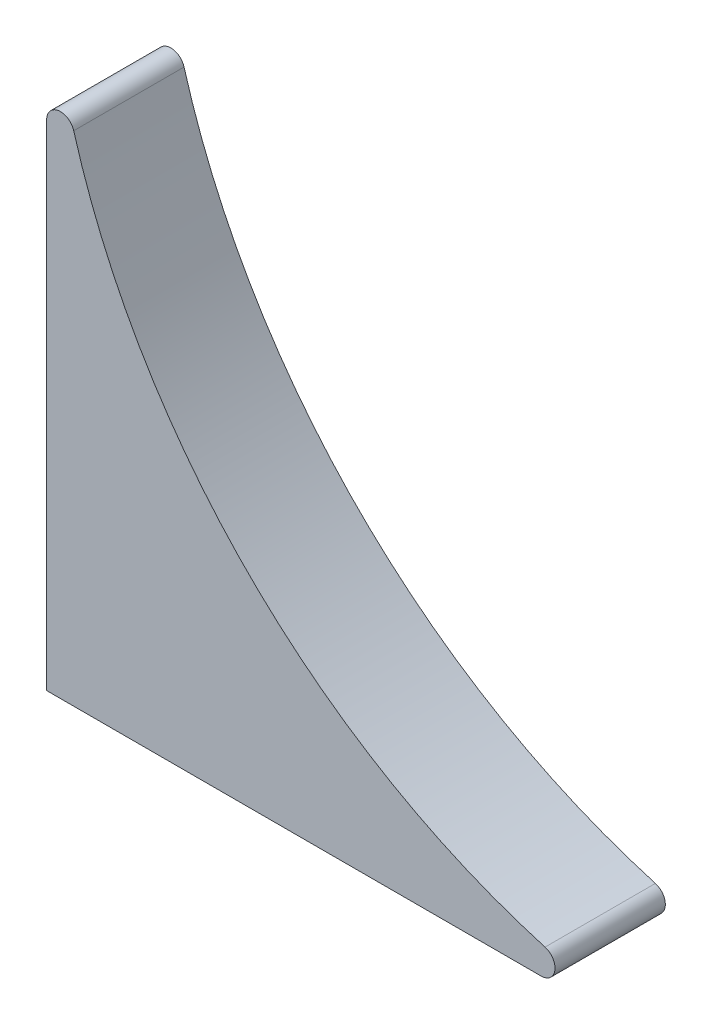
SolidWorks part; units mm, degrees
ref_plane "Ebene vorne" through (0, 0, 0) normal (0, 0, 1) x (1, 0, 0)
ref_plane "Ebene oben" through (0, 0, 0) normal (0, 1, 0) x (1, 0, 0)
ref_plane "Ebene rechts" through (0, 0, 0) normal (1, 0, 0) x (0, 0, -1)
sketch "Skizze1" plane through (0, 0, 0) normal (0, 0, 1) x (1, 0, 0)
  line L1 (0, 0) -> (25, 0)
  line L2 (0, 0) -> (0, 25)
  arc A0 (0, 25) -> (25, 0) centre (25, 25) ccw
  dimension "D1" = 25
  dimension "D2" = 25
  dimension "D3" = 25
extrude "Aufsatz-Linear austragen1" add sketch "Skizze1" along normal blind 4
fillet "Verrundung1" radius 0.5 2 edges at (25, 0, 2) (0, 25, 2)
